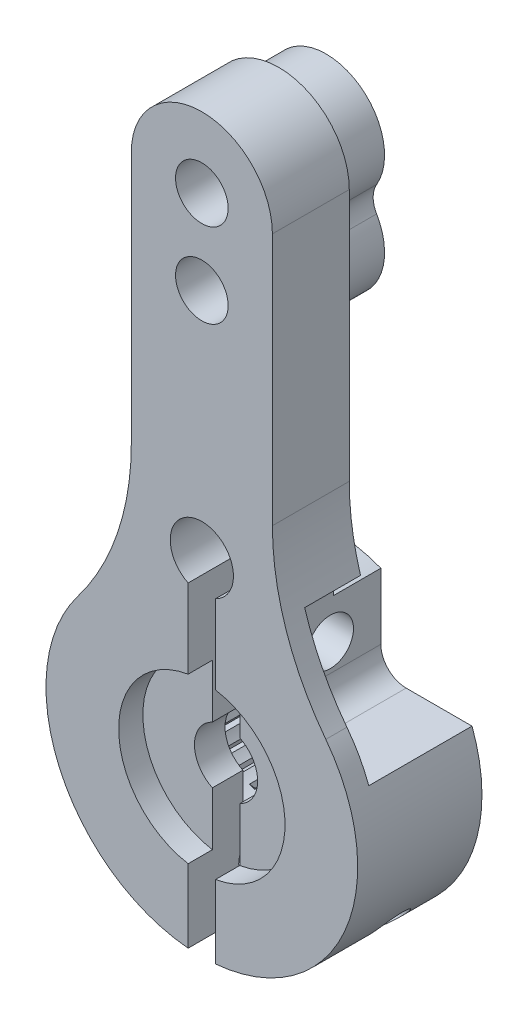
SolidWorks part; units mm, degrees
material "6061 Alloy"
ref_plane "Front Plane" through (0, 0, 0) normal (0, 0, 1) x (1, 0, 0)
ref_plane "Top Plane" through (0, 0, 0) normal (0, 1, 0) x (1, 0, 0)
ref_plane "Right Plane" through (0, 0, 0) normal (1, 0, 0) x (0, 0, -1)
sketch "Sketch1" plane through (0, 0, 0) normal (0, 0, 1) x (1, 0, 0)
  line L0 (0, 0) -> (0, 24) construction
  line L1 (-3.35, 0) -> (-3.35, 24)
  line L2 (3.35, 0) -> (3.35, 24)
  circle A0 centre (0, 0) radius 7.4
  arc A1 (-3.35, 0) -> (3.35, 0) centre (0, 0) ccw
  arc A2 (3.35, 24) -> (-3.35, 24) centre (0, 24) ccw
  arc A3 (3.35, 12) -> (5.8866, 4.4842) centre (15.7528, 12) ccw
  arc A4 (-3.35, 12) -> (-5.8866, 4.4842) centre (-15.7528, 12) cw
  point P4 (0, 12)
  dimension "D1" = 14.8
  dimension "D2" = 24
  dimension "D3" = 6.7
extrude "Boss-Extrude1" add sketch "Sketch1" along normal blind 3.65 contours L2 A2 L1 A0 | L1 A1 L2 A0 | A1 L1 A0 L2 | L1 A4 A0 | A3 L2 A0 region at (0, 16.8979, 0) region at (-3.9265, 7.4438, 0) region at (0, 2.2281, 0) region at (-3.5537, 3.2991, 0) region at (3.9265, 7.4438, 0)
hole_wizard "Ø3.0 (3) Diameter Hole1" positions "Sketch3" profile "Sketch4" hole size "Ø3.0" standard "BSI" end condition up to next
sketch "Sketch3" plane through (0, 0, 3.65) normal (0, 0, 1) x (1, 0, 0)
  line L0 (0, 9) -> (0, 0) construction
  circle A0 centre (0, 0) radius 7.4
  point P0 (0, 0)
  point P4 (0, 9)
  dimension "D1" = 9
sketch "Sketch4" plane through (0, 0, 3.65) normal (1, 0, 0) x (0, -1, 0)
  line L0 (0, 0) -> (0, 3.65)
  line L1 (0, 3.65) -> (1.5, 3.65)
  line L2 (1.5, 3.65) -> (1.5, 0)
  line L5 (1.5, 0) -> (0, 0)
  line L11 (0, -6.35) -> (0, 107.95) construction
  dimension "Thru Hole Dia." = 3
  dimension "Thru Hole Depth" = 3.65
ref_axis "Axis1" through (0, 0, 0) along (0, 0, 1)
hole_wizard "Tap Drill for M3x0.5 Tap1" positions "Sketch7" profile "Sketch6" hole size "M3x0.5" standard "BSI" end condition up to next
sketch "Sketch7" plane through (0, 0, 3.65) normal (0, 0, 1) x (1, 0, 0)
  line L0 (0, 24) -> (0, 20) construction
  point P0 (0, 24)
  point P3 (0, 20)
  dimension "D1" = 20
sketch "Sketch6" plane through (0, 24, 3.65) normal (1, 0, 0) x (0, -1, 0)
  line L0 (0, 0) -> (0, 3.65)
  line L1 (0, 3.65) -> (1.25, 3.65)
  line L2 (1.25, 3.65) -> (1.25, 0)
  line L5 (1.25, 0) -> (0, 0)
  line L11 (0, -6.35) -> (0, 107.95) construction
  dimension "Thru Hole Dia." = 2.5
  dimension "Thru Hole Depth" = 3.65
cosmetic thread "Cosmetic Thread2" parameters "D2"=3
cosmetic thread "Cosmetic Thread3" parameters "D2"=3
sketch "Sketch10" plane through (0, 0, 0) normal (0, 0, -1) x (-1, 0, 0)
  line L0 (0, 24) -> (0, 20) construction
  line L1 (2.775, 24) -> (2.775, 20)
  line L2 (-2.775, 24) -> (-2.775, 20)
  circle A0 centre (0, 0) radius 7.4
  arc A1 (2.775, 24) -> (-2.775, 24) centre (0, 24) ccw
  arc A2 (-2.775, 20) -> (2.775, 20) centre (0, 20) ccw
  circle A3 centre (0, 0) radius 1.5 construction
  circle A4 centre (0, 20) radius 1.25 construction
  circle A5 centre (0, 24) radius 1.25 construction
  circle A6 centre (0, 0) radius 1.5
  circle A7 centre (0, 20) radius 1.25
  circle A8 centre (0, 24) radius 1.25
  arc A9 (-2.775, 24) -> (2.775, 24) centre (0, 24) ccw
  arc A10 (-2.775, 20) -> (2.775, 20) centre (0, 20) cw
  point P8 (0, 22)
  circle M3 centre (0, 24) radius 1.25
  circle M4 centre (0, 20) radius 1.25
  circle M5 centre (0, 0) radius 1.5
  arc M12 (-5.8866, 4.4842) -> (5.8866, 4.4842) centre (0, 0) ccw
  dimension "D1" = 5.55
extrude "Boss-Extrude3" add sketch "Sketch10" along normal blind 2.25 contours A9 A10 A8 A1 | A10 A2 A9 A7 | L0 A8 A10 A9 M4 | L0 A7 A9 A10 M3 | A0 M12 M5 region at (-0.7392, 22, 0) region at (0.7392, 22, 0) region at (1.1622, 22.6003, 0) region at (1.1622, 21.3997, 0) region at (2.2994, -6.8131, 0)
sketch "Sketch9" plane through (0, 0, 3.65) normal (0, 0, 1) x (1, 0, 0)
  line L1 (-0.65, -8.3704) -> (0.65, -8.3704)
  line L2 (-0.65, -8.3704) -> (-0.65, 8.3704)
  line L3 (-0.65, 8.3704) -> (0.65, 8.3704)
  line L4 (0.65, -8.3704) -> (0.65, 8.3704)
  line L5 (-0.65, -8.3704) -> (0.65, 8.3704) construction
  line L6 (-0.65, 8.3704) -> (0.65, -8.3704) construction
  point P0 (0, 0)
  dimension "D1" = 1.3
extrude "Cut-Extrude2" cut sketch "Sketch9" against normal through all
sketch "Sketch11" plane through (0, 0, -2.25) normal (0, 0, -1) x (-1, 0, 0)
  line L0 (-2.6, 8.4) -> (-0.5, 8.4) construction
  line L1 (-2.6, 8.4) -> (-9.2657, 8.4)
  line L2 (-2.6, 8.4) -> (-2.6, 2.6)
  line L3 (-2.6, 2.6) -> (-9.2657, 2.6)
  line L4 (-9.2657, 8.4) -> (-9.2657, 2.6)
  line L5 (-9.2657, 5.5) -> (-0.65, 5.5) construction
  line L6 (-0.65, 7.3714) -> (-0.65, 1.3519) construction
  arc A0 (0.65, -7.3714) -> (0.65, 7.3714) centre (0, 0) ccw construction
  circle A1 centre (0, 0) radius 7.4 construction
  arc A2 (-0.65, 7.3714) -> (-5.8866, 4.4842) centre (0, 0) ccw construction
  point P4 (7.4, 0)
  point P17 (0, -7.4)
  dimension "D1" = 10
  dimension "D2" = 5.8
  dimension "D3" = 10
extrude "Cut-Extrude3" cut sketch "Sketch11" against normal blind 4.9
pattern_circular "CirPattern3" count 2 over 360 about axis through (0, 0, 0) along (0, 0, 1) of "Cut-Extrude3"
hole_wizard "M2 Clearance Hole1" positions "Sketch14" profile "Sketch13" hole size "M2" standard "BSI" end condition up to next
sketch "Sketch14" plane through (2.6, 0, 0) normal (1, 0, 0) x (0, 0, -1)
  line L0 (-2.65, 5.1) -> (-0.15, 5.1) construction
  line L2 (-0.15, 5.1) -> (-0.15, 2.6) construction
  line L4 (-2.65, 4.4842) -> (-2.65, 8.4) construction
  line L5 (2.25, 2.6) -> (-2.65, 2.6) construction
  point P0 (-0.15, 5.1)
  dimension "D1" = 2.5
  dimension "D2" = 2.5
sketch "Sketch13" plane through (2.6, 5.1, 0.15) normal (0, 1, 0) x (0, 0, -1)
  line L0 (0, 0) -> (0, 1.95)
  line L1 (0, 1.95) -> (1.1, 1.95)
  line L2 (1.1, 1.95) -> (1.1, 0)
  line L5 (1.1, 0) -> (0, 0)
  line L11 (0, -6.35) -> (0, 107.95) construction
  dimension "Thru Hole Dia." = 2.2
  dimension "Thru Hole Depth" = 1.95
hole_wizard "M2 Clearance Hole2" positions "Sketch20" profile "Sketch21" hole size "M2" standard "BSI" end condition up to next
sketch "Sketch20" plane through (-2.6, 0, 0) normal (-1, 0, 0) x (0, 0, 1)
  line L1 (0.15, 5.1) -> (0.15, -5.1) construction
  line L3 (0, 0) -> (3.65, 0) construction
  point P0 (0.15, -5.1)
  point P8 (0.15, 0)
sketch "Sketch21" plane through (-2.6, -5.1, 0.15) normal (0, 1, 0) x (0, 0, 1)
  line L0 (0, 0) -> (0, 1.95)
  line L1 (0, 1.95) -> (1.1, 1.95)
  line L2 (1.1, 1.95) -> (1.1, 0)
  line L5 (1.1, 0) -> (0, 0)
  line L11 (0, -6.35) -> (0, 107.95) construction
  dimension "Thru Hole Dia." = 2.2
  dimension "Thru Hole Depth" = 1.95
hole_wizard "Tap Drill for M2x0.4 Tap1" positions "Sketch15" profile "Sketch16" hole size "M2x0.4" standard "BSI" end condition through all
sketch "Sketch15" plane through (-0.65, 0, 0) normal (1, 0, 0) x (0, 0, -1)
  point P0 (-0.15, 5.1)
sketch "Sketch16" plane through (-0.65, 5.1, 0.15) normal (0, 1, 0) x (0, 0, -1)
  line L0 (0, 0) -> (0, 6.75)
  line L1 (0, 6.75) -> (0.8, 6.75)
  line L2 (0.8, 6.75) -> (0.8, 0)
  line L5 (0.8, 0) -> (0, 0)
  line L11 (0, -6.35) -> (0, 107.95) construction
  dimension "Thru Hole Dia." = 1.6
  dimension "Thru Hole Depth" = 6.75
cosmetic thread "Cosmetic Thread1" parameters "D2"=2.5
hole_wizard "Tap Drill for M2x0.4 Tap2" positions "Sketch22" profile "Sketch23" hole size "M2x0.4" standard "BSI" end condition through all
sketch "Sketch22" plane through (0.65, 0, 0) normal (-1, 0, 0) x (0, 0, 1)
  point P0 (0.15, -5.1)
sketch "Sketch23" plane through (0.65, -5.1, 0.15) normal (0, 1, 0) x (0, 0, 1)
  line L0 (0, 0) -> (0, 6.75)
  line L1 (0, 6.75) -> (0.8, 6.75)
  line L2 (0.8, 6.75) -> (0.8, 0)
  line L5 (0.8, 0) -> (0, 0)
  line L11 (0, -6.35) -> (0, 107.95) construction
  dimension "Thru Hole Dia." = 1.6
  dimension "Thru Hole Depth" = 6.75
fillet "Fillet3" radius 1.2 3 edges at (2.6, 8.4, 1.325) (2.6, 2.6, 0.2) (-2.6, -2.6, 0.2)
sketch "Sketch8" plane through (0, 0, 3.65) normal (0, 0, 1) x (1, 0, 0)
  circle A0 centre (0, 0) radius 3.95
  dimension "D1" = 7.9
extrude "Cut-Extrude1" cut sketch "Sketch8" against normal blind 1.15
sketch "Sketch17" plane through (0, 0, -2.25) normal (0, 0, -1) x (-1, 0, 0)
  circle A0 centre (0, 0) radius 2.95
  dimension "D1" = 5.9
extrude "Boss-Extrude4" add sketch "Sketch17" against normal blind 3.3 separate body
sketch "Sketch24" plane through (0, 0, -2.25) normal (0, 0, -1) x (-1, 0, 0)
  line L0 (-0.0404, 3.1747) -> (-0.5215, 2.3415)
  line L1 (-0.5215, 2.3415) -> (0.4407, 2.3415)
  line L2 (0.4407, 2.3415) -> (-0.0404, 3.1747)
  circle A0 centre (0, 0) radius 3.175 construction
  dimension "D1" = 6.35
extrude "Boss-Extrude5" add sketch "Sketch24" against normal blind 3 separate body
draft "Draft2" type of draft neutral plane draft angle 45 faces to draft 1 face at (0.0404, 2.6192, 0.75) neutral plane through (0.5215, 2.3415, 0.75) neutral plane normal (0, -1, 0) reverse direction yes parameters "D1"=45
pattern_circular "CirPattern4" count 25 over 360 about axis through (0, 0, 0) along (0, 0, 1) of bodies 119
combine bodies "Combine1" operation type add bodies to combine 119 120 121 122 123 124 125 126 127 128 129 130 131 132 133 134 135 136 137 138 139 140 141 142 143 118
combine bodies "Combine2" operation type subtract main body 104 bodies to subtract 144
fillet "Fillet4" radius 1.2 2 edges at (-1.9237, 22, -1.125) (1.9237, 22, -1.125)
